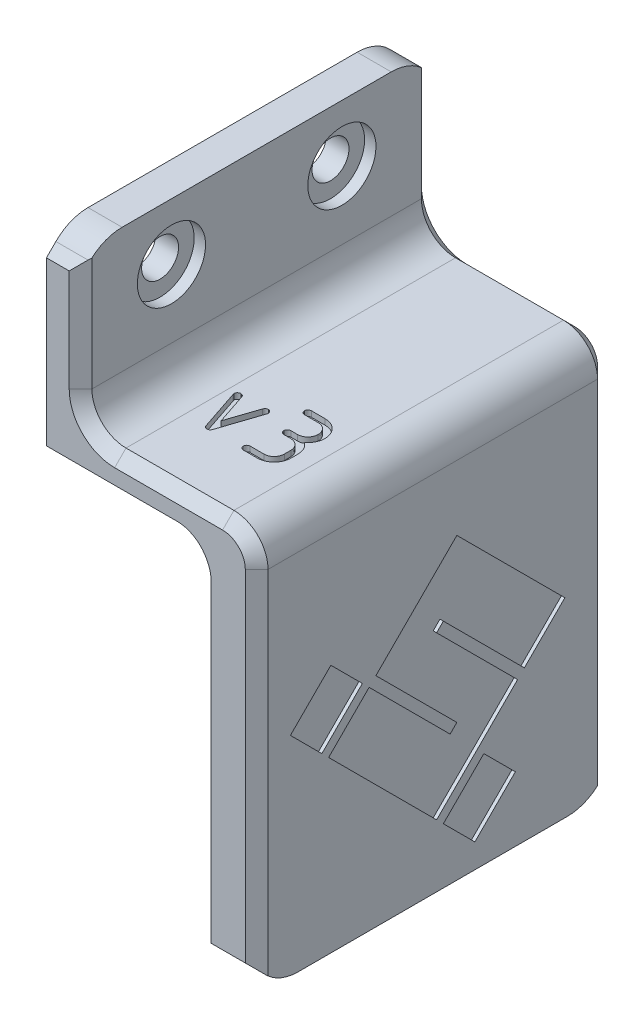
SolidWorks part; units mm, degrees
other "DetailItem1"
other "DetailItem2"
material "ABS_eSun_GRN"
ref_plane "Front Plane" through (0, 0, 0) normal (0, 0, 1) x (1, 0, 0)
ref_plane "Top Plane" through (0, 0, 0) normal (0, 1, 0) x (1, 0, 0)
ref_plane "Right Plane" through (0, 0, 0) normal (1, 0, 0) x (0, 0, -1)
sketch "Sketch1" plane through (0, 0, 0) normal (0, 0, 1) x (1, 0, 0)
  line L0 (0, 18) -> (0, 36)
  line L1 (0, 36) -> (3, 36)
  line L2 (3, 36) -> (3, 22)
  line L3 (3, 22) -> (18.5, 22)
  line L4 (18.5, 22) -> (18.5, -13)
  line L5 (18.5, -13) -> (14.5, -13)
  line L6 (14.5, -13) -> (14.5, 18)
  line L7 (14.5, 18) -> (0, 18)
  line L8 (3, 31) -> (0, 31) construction
  line L9 (18.5, 0) -> (0, 0) construction
  dimension "D1" = 3
  dimension "D3" = 31
  dimension "D4" = 14
  dimension "D6" = 14.5
  dimension "D2" = 4
  dimension "D5" = 4
  dimension "D8" = 31
  dimension "D7" = 18
extrude "bossMain" add sketch "Sketch1" along normal mid plane 31
sketch "Sketch2" plane through (14.5, 0, 0) normal (-1, 0, 0) x (0, 0, 1)
  line L0 (0, 18) -> (0, -13) construction
  line L1 (15.5, 18) -> (-15.5, 18) construction
  line L2 (15.5, -13) -> (-15.5, -13) construction
  line L4 (-5.58, -9.075) -> (5.58, -9.075) construction
  line L6 (-5.58, -9.075) -> (-5.58, 9.075) construction
  line L7 (-5.58, 9.075) -> (5.58, 9.075) construction
  line L8 (5.58, -9.075) -> (5.58, 9.075) construction
  line L9 (-5.58, -9.075) -> (5.58, 9.075) construction
  line L10 (-5.58, 9.075) -> (5.58, -9.075) construction
  circle A1 centre (5.58, 9.075) radius 0.75
  circle A2 centre (-5.58, -9.075) radius 0.75
  point P0 (0, 0)
  point P4 (0, 2.5)
  dimension "D1" = 1.5
  dimension "D3" = 11.16
  dimension "D4" = 18.15
  dimension "D6" = 2.5
extrude "encoderHoles" cut sketch "Sketch2" against normal offset from surface (3.6 mm away) 0.4 up to face at (18.5, 4.5, 0)
sketch "Sketch_Sensor_Locale" plane through (14.5, 0, 0) normal (-1, 0, 0) x (0, 0, 1)
  line L0 (-5.58, -9.075) -> (0, 0) construction
  line L1 (-2.15, -2.6) -> (2.15, -2.6)
  line L2 (-2.15, -2.6) -> (-2.15, 2.6)
  line L3 (-2.15, 2.6) -> (2.15, 2.6)
  line L4 (2.15, -2.6) -> (2.15, 2.6)
  line L5 (-2.15, -2.6) -> (2.15, 2.6) construction
  line L6 (-2.15, 2.6) -> (2.15, -2.6) construction
  line L7 (0, 0) -> (5.58, 9.075) construction
  line L8 (15.5, 18) -> (-15.5, 18) construction
  point P0 (0, 0)
  dimension "D1" = 4.3
  dimension "D2" = 5.2
  dimension "D3" = 18
sketch "Sketch3" plane through (3, 0, 0) normal (1, 0, 0) x (0, 0, -1)
  line L0 (-7.5, 31) -> (7.5, 31) construction
  line L1 (-15.5, 36) -> (15.5, 36) construction
  line L2 (-5.58, 9.075) -> (5.58, -9.075) construction
  circle A0 centre (-7.5, 31) radius 1.625
  circle A1 centre (7.5, 31) radius 1.625
  point P4 (0, 31)
  point P7 (0, 36)
  point P12 (0, 0)
  dimension "D2" = 3.25
  dimension "D1" = 15
  dimension "D3" = 31
extrude "cut mounting holes M2.5" cut sketch "Sketch3" against normal through all
sketch "Sketch4" plane through (0, 0, 0) normal (-1, 0, 0) x (0, 0, 1)
  line L0 (-15.5, 18) -> (-15.5, 16)
  line L1 (-15.5, 18) -> (-15.5, -13) construction
  line L2 (-15.5, 18) -> (15.5, 18)
  line L3 (15.5, 18) -> (15.5, 16)
  line L4 (15.5, 18) -> (15.5, -13) construction
  line L5 (15.5, 18) -> (15.5, -13) construction
  arc A0 (-15.5, 16) -> (15.5, 16) centre (0, -52.2624) cw
  dimension "D1" = 70
  dimension "D2" = 2
extrude "bossCurve" add sketch "Sketch4" against normal up to surface (14.5 mm away) up to face at (14.5, -9.075, -4.83)
fillet "filletBody" radius 3 2 edges at (3, 22, 0) (18.5, 22, 0)
chamfer "chamf_Shoulder_bottom" distance 7.5 angle 30 1 edges at (7.25, 16, -15.5) first distance on face at (7.25, 16.8688, 0)
chamfer "Chamfer1" distance 7 angle 30 1 edges at (7.25, 16, 15.5) first distance on face at (7.25, 17.1469, 4.1645)
fillet "filletInside" radius 3 3 edges at (14.5, 18.6447, -11.3634) (14.5, 17.7369, 0.3149) (14.5, 18.4799, 11.6764)
chamfer "chamferShoulders" distance 2 angle 45 4 edges at (16.5, -13, 15.5) (16.5, -13, -15.5) (1.5, 36, -15.5) (1.5, 36, 15.5)
fillet "Fillet3" radius 10 4 edges at (13.3453, 16.7188, -7.2901) (5.75, 17.3636, -7.2268) (13.344, 16.6511, 7.9133) (5.75, 17.2958, 7.8528)
sketch "Sketch9" plane through (14.5, 0, 0) normal (-1, 0, 0) x (0, 0, 1)
  line L0 (0, 11.3) -> (0, -11.3) construction
  line L1 (-6, 11.3) -> (6, 11.3)
  line L2 (-6, 11.3) -> (-6, 12.55)
  line L3 (-6, 12.55) -> (6, 12.55)
  line L4 (6, 11.3) -> (6, 12.55)
  line L5 (13.5, -13) -> (-13.5, -13) construction
  line L6 (-6, -13) -> (6, -13)
  line L7 (-6, -13) -> (-6, -11.3)
  line L8 (-6, -11.3) -> (6, -11.3)
  line L9 (6, -13) -> (6, -11.3)
  dimension "D3" = 12
  dimension "D4" = 1.25
  dimension "D1" = 22.6
extrude "boss datum bumps" add sketch "Sketch9" along normal blind 1
sketch "Sketch11" plane through (0, 22, 0) normal (0, 1, 0) x (1, 0, 0)
  line L0 (6, -9.5) -> (15.5, -9.5) construction
  line L1 (6, 15.5) -> (6, -15.5) construction
  line L2 (15.5, -15.5) -> (15.5, 15.5) construction
  line L3 (15.5, -15.5) -> (6, -15.5) construction
  text T0 "v3" font "DS ISO 1" height 6
  dimension "D1" = 6
extrude "version" cut sketch "Sketch11" against normal blind 0.5
chamfer "chamferMain" distance 1 angle 45 10 edges at (18.5, 4, 15.5) (3, 29.5, 15.5) (17.6213, 21.1213, 15.5) (3.8787, 22.8787, 15.5) (10.75, 22, 15.5) (18.5, 4, -15.5) (3, 29.5, -15.5) (17.6213, 21.1213, -15.5) (3.8787, 22.8787, -15.5) (10.75, 22, -15.5)
chamfer "chamfer Datums" distance 1 angle 45 4 edges at (13.5, 11.925, -6) (13.5, 11.925, 6) (13.5, -12.15, -6) (13.5, -12.15, 6)
chamfer "chamferEncoder" distance 0.6 angle 45 2 edges at (14.5, 9.075, 6.33) (14.5, -9.075, -4.83)
sketch "Sketch12" plane through (18.5, 0, 0) normal (1, 0, 0) x (0, 0, -1)
  line L0 (7.2665, -7.3083) -> (3.7027, -10.8721)
  line L1 (4.4946, -4.5365) -> (7.2665, -7.3083)
  line L2 (0.9308, -8.1003) -> (4.4946, -4.5365)
  line L3 (3.7027, -10.8721) -> (0.9308, -8.1003)
  line L4 (1.5248, -1.5666) -> (2.1187, -0.9726)
  line L5 (-5.6029, 5.561) -> (1.5248, -1.5666)
  line L6 (-9.1667, 1.9972) -> (-5.6029, 5.561)
  line L7 (0.3368, -7.5063) -> (-9.1667, 1.9972)
  line L8 (7.4645, -0.3787) -> (0.3368, -7.5063)
  line L9 (0.3368, 6.749) -> (7.4645, -0.3787)
  line L10 (0.9308, 7.3429) -> (0.3368, 6.749)
  line L11 (11.6223, 3.7791) -> (8.0584, 0.2153)
  line L12 (2.1187, 13.2826) -> (11.6223, 3.7791)
  line L13 (-5.0089, 6.155) -> (2.1187, 13.2826)
  line L14 (2.1187, -0.9726) -> (-5.0089, 6.155)
  line L15 (-9.7607, 2.5912) -> (-12.5325, 5.363)
  line L16 (-6.1968, 6.155) -> (-9.7607, 2.5912)
  line L17 (-8.9687, 8.9268) -> (-6.1968, 6.155)
  line L18 (-12.5325, 5.363) -> (-8.9687, 8.9268)
  line L19 (14.0651, 15.7254) -> (-13.9349, 15.7254) construction
  line L20 (14.0651, -12.2746) -> (14.0651, 15.7254) construction
  line L21 (-13.9349, -12.2746) -> (14.0651, -12.2746) construction
  line L22 (-13.9349, 15.7254) -> (-13.9349, -12.2746) construction
  line L23 (8.0584, 0.2153) -> (0.9308, 7.3429)
  point P24 (0.0651, 15.7254)
extrude "cut logo" cut sketch "Sketch12" against normal blind 0.3
fillet "Fillet4" radius 4 4 edges at (1.5, 36, -13.5) (1.5, 36, 13.5) (16.5, -13, 13.5) (16.5, -13, -13.5)
sketch "Sketch13" plane through (3, 0, 0) normal (1, 0, 0) x (0, 0, -1)
  circle A0 centre (-7.5, 31) radius 3
  circle A1 centre (7.5, 31) radius 3
  dimension "D1" = 6
extrude "counterBoreMtHoles" cut sketch "Sketch13" against normal blind 1
equation "\"encoderGap\"= 22.6"
equation "\"D1@Sketch9\"=\"encoderGap\""
equation "\"reach\"=14.5"
equation "\"D6@Sketch1\"=\"reach\""
equation "\"D5@Sketch1\"=\"D2@Sketch1\""
